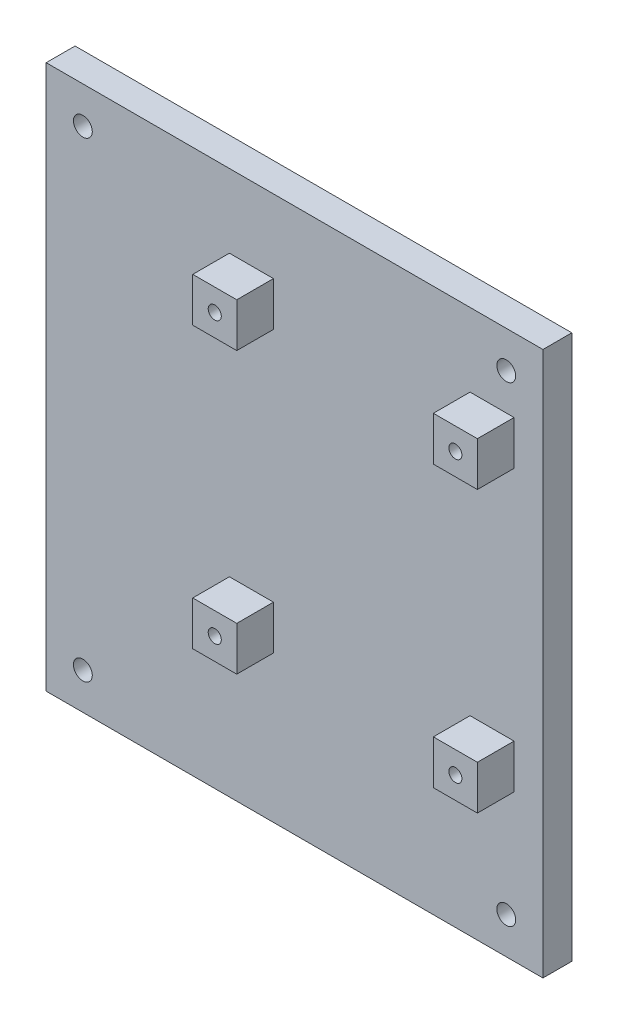
SolidWorks part; units mm, degrees
ref_plane "Front Plane" through (0, 0, 0) normal (0, 0, 1) x (1, 0, 0)
ref_plane "Top Plane" through (0, 0, 0) normal (0, 1, 0) x (1, 0, 0)
ref_plane "Right Plane" through (0, 0, 0) normal (1, 0, 0) x (0, 0, -1)
sketch "Sketch1" plane through (0, 0, 0) normal (0, 0, 1) x (1, 0, 0)
  line L1 (-43, -47.117) -> (43, -47.117)
  line L2 (-43, -47.117) -> (-43, 47.117)
  line L3 (-43, 47.117) -> (43, 47.117)
  line L4 (43, -47.117) -> (43, 47.117)
  line L5 (-43, -47.117) -> (43, 47.117) construction
  line L6 (-43, 47.117) -> (43, -47.117) construction
  point P0 (0, 0)
  dimension "D1" = 86
  dimension "D2" = 94.234
extrude "Boss-Extrude1" add sketch "Sketch1" along normal blind 5
sketch "Sketch2" plane through (0, 0, 5) normal (0, 0, 1) x (1, 0, 0)
  line L0 (43, 47.117) -> (-43, 47.117) construction
  line L1 (-11.276, 34.417) -> (-3.656, 34.417)
  line L2 (-11.276, 34.417) -> (-11.276, 26.797)
  line L3 (-11.276, 26.797) -> (-3.656, 26.797)
  line L4 (-3.656, 34.417) -> (-3.656, 26.797)
  line L5 (30.38, 34.417) -> (38, 34.417)
  line L6 (30.38, 34.417) -> (30.38, 26.797)
  line L7 (30.38, 26.797) -> (38, 26.797)
  line L8 (38, 34.417) -> (38, 26.797)
  line L9 (-11.276, -14.097) -> (-3.656, -14.097)
  line L10 (-11.276, -14.097) -> (-11.276, -21.717)
  line L11 (-11.276, -21.717) -> (-3.656, -21.717)
  line L12 (-3.656, -14.097) -> (-3.656, -21.717)
  line L13 (30.38, -14.097) -> (38, -14.097)
  line L14 (30.38, -14.097) -> (30.38, -21.717)
  line L15 (30.38, -21.717) -> (38, -21.717)
  line L16 (38, -14.097) -> (38, -21.717)
  line L18 (43, -47.117) -> (43, 47.117) construction
  dimension "D1" = 7.62
  dimension "D2" = 12.7
  dimension "D3" = 5
  dimension "D4" = 49.276
  dimension "D5" = 56.134
extrude "Boss-Extrude2" add sketch "Sketch2" along normal blind 6.35
hole_wizard "#4-40 Tapped Hole1" positions "Sketch3" profile "Sketch4" tap size "#4-40" standard "ANSI Inch"
sketch "Sketch3" plane through (0, 0, 11.35) normal (0, 0, 1) x (1, 0, 0)
  line L0 (-3.656, 34.417) -> (-11.276, 34.417) construction
  line L1 (-11.276, 34.417) -> (-11.276, 26.797) construction
  line L2 (38, 34.417) -> (30.38, 34.417) construction
  line L3 (30.38, 34.417) -> (30.38, 26.797) construction
  line L4 (-3.656, -14.097) -> (-11.276, -14.097) construction
  line L5 (-11.276, -14.097) -> (-11.276, -21.717) construction
  line L6 (38, -14.097) -> (30.38, -14.097) construction
  line L7 (30.38, -14.097) -> (30.38, -21.717) construction
  point P0 (-7.466, 30.607)
  point P2 (34.19, 30.607)
  point P4 (-7.466, -17.907)
  point P6 (34.19, -17.907)
  point P12 (-7.466, 34.417)
  point P16 (-11.276, 30.607)
  point P20 (34.19, 34.417)
  point P24 (30.38, 30.607)
  point P28 (-7.466, -14.097)
  point P32 (-11.276, -17.907)
  point P36 (34.19, -14.097)
  point P40 (30.38, -17.907)
sketch "Sketch4" plane through (-7.466, 30.607, 11.35) normal (1, 0, 0) x (0, -1, 0)
  line L0 (0, 0) -> (0, 5.429)
  line L1 (0, 5.429) -> (1.1303, 4.7498)
  line L2 (1.1303, 4.7498) -> (1.1303, 0)
  line L5 (1.1303, 0) -> (0, 0)
  line L10 (0, 5.429) -> (-1.1303, 4.7498) construction
  line L11 (0, -6.35) -> (0, 107.95) construction
  dimension "Tap Drill Dia." = 2.2606
  dimension "Tap Drill Depth" = 4.7498
  dimension "Drill Angle" = 118
cosmetic thread "Hole Thread1" parameters "D1"=5.588, "D2"=2.8448
cosmetic thread "Hole Thread2" parameters "D1"=5.588, "D2"=2.8448
cosmetic thread "Hole Thread3" parameters "D1"=5.588, "D2"=2.8448
cosmetic thread "Hole Thread4" parameters "D1"=5.588, "D2"=2.8448
hole_wizard "#4 Clearance Hole1" positions "Sketch5" profile "Sketch6" hole size "#4" standard "ANSI Inch" end condition through all
sketch "Sketch5" plane through (0, 0, 5) normal (0, 0, 1) x (1, 0, 0)
  line L0 (-43, 47.117) -> (-43, -47.117) construction
  line L1 (43, 47.117) -> (-43, 47.117) construction
  line L2 (43, -47.117) -> (43, 47.117) construction
  line L3 (-43, -47.117) -> (43, -47.117) construction
  point P0 (-36.65, 40.767)
  point P2 (36.65, 40.767)
  point P4 (-36.65, -40.767)
  point P6 (36.65, -40.767)
  dimension "D1" = 6.35
  dimension "D2" = 6.35
  dimension "D3" = 6.35
  dimension "D4" = 6.35
  dimension "D5" = 6.35
  dimension "D6" = 6.35
  dimension "D7" = 6.35
  dimension "D8" = 6.35
sketch "Sketch6" plane through (-36.65, 40.767, 5) normal (1, 0, 0) x (0, -1, 0)
  line L0 (0, 0) -> (0, 5)
  line L1 (0, 5) -> (1.6319, 5)
  line L2 (1.6319, 5) -> (1.6319, 0)
  line L5 (1.6319, 0) -> (0, 0)
  line L11 (0, -6.35) -> (0, 107.95) construction
  dimension "Thru Hole Dia." = 3.2639
  dimension "Thru Hole Depth" = 5
equation "\"PCB Width\"= 1940mil"
equation "\"PCB Height\"= 2210mil"
equation "\"PCB Thickness\"= 63mil"
equation "\"PCB Mount Height\"= 0.25in"
equation "\"Motor Body Front Diameter\"= 37mm"
equation "\"Motor Body Front Length\"= 30mm"
equation "\"Motor Bearing Length\"= 5mm"
equation "\"Motor Body Back Length\"= 33.3mm"
equation "\"Motor PCR\"= 31mm / 2"
equation "\"Large PVC Fittings Wall Thickness\"= 15in / 64"
equation "\"Large PVC Pipe Outer Diameter\"= 3.5in"
equation "\"Box Width\"= 2 * \"Motor Bearing Length\" + \"Motor Body Front Length\" + \"Motor Body Back Length\" + 0.5in"
equation "\"Box Hole Center to Edge Distance\"= 250mil"
equation "\"Box Ceiling and Floor Thickness\"= 2 * \"Box Hole Center to Edge Distance\""
equation "\"Box Height\"= 2 * \"Box Ceiling and Floor Thickness\" + \"PCB Height\" + 0.5in"
equation "\"Box Middle Depth\"= \"Large PVC Fittings Wall Thickness\" + \"Large PVC Pipe Outer Diameter\" / 2 + \"Motor Body Front Diameter\" / 2 - \"Motor Bearing Length\""
equation "\"D1@Sketch1\"=\"Box Width\" "
equation "\"D2@Sketch1\"=\"Box Height\""
equation "\"D1@Boss-Extrude1\"=\"Motor Bearing Length\""
equation "\"D2@Sketch2\"=\"Box Ceiling and Floor Thickness\""
equation "\"D3@Sketch2\"=\"Motor Bearing Length\""
equation "\"D4@Sketch2\"=\"PCB Width\""
equation "\"D5@Sketch2\"=\"PCB Height\""
equation "\"D1@Boss-Extrude2\"=\"PCB Mount Height\""
equation "\"Tap Drill Depth@Sketch4\"=0.25in - \"PCB Thickness\""
equation "\"D1@Sketch5\"=\"Box Hole Center to Edge Distance\""
equation "\"D2@Sketch5\"=\"Box Hole Center to Edge Distance\""
equation "\"D3@Sketch5\"=\"Box Hole Center to Edge Distance\""
equation "\"D4@Sketch5\"=\"Box Hole Center to Edge Distance\""
equation "\"D5@Sketch5\"=\"Box Hole Center to Edge Distance\""
equation "\"D6@Sketch5\"=\"Box Hole Center to Edge Distance\""
equation "\"D7@Sketch5\"=\"Box Hole Center to Edge Distance\""
equation "\"D8@Sketch5\"=\"Box Hole Center to Edge Distance\""
